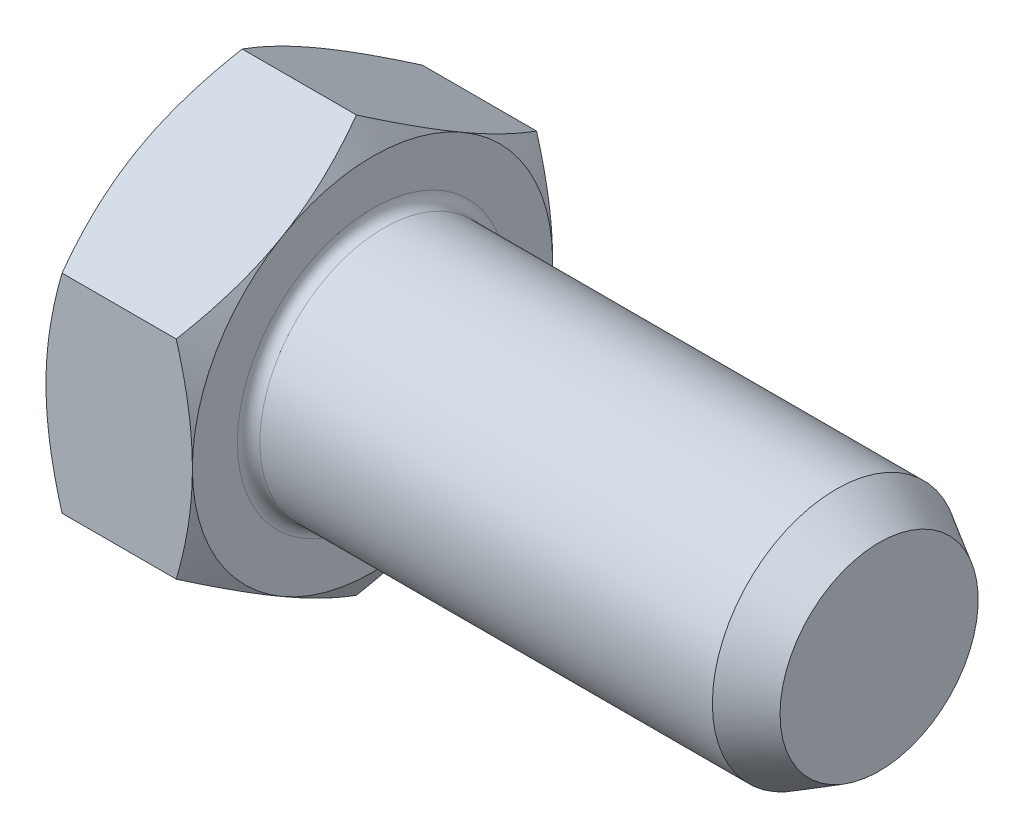
SolidWorks part; units mm, degrees
ref_plane "Front" through (0, 0, 0) normal (0, 0, 1) x (1, 0, 0)
ref_plane "Top" through (0, 0, 0) normal (0, 1, 0) x (1, 0, 0)
ref_plane "Right" through (0, 0, 0) normal (1, 0, 0) x (0, 0, -1)
sketch "Sketch1" plane through (0, 0, 0) normal (0, 0, 1) x (1, 0, 0)
  line L0 (0, 0) -> (0, 1.4)
  line L1 (0, 1.4) -> (1.3, 1.4)
  line L2 (1.3, 1.4) -> (1.3, 1.1)
  line L4 (1.3, 1.1) -> (5.8, 1.1)
  line L5 (5.8, 1.1) -> (5.8, 0)
  line L6 (5.8, 0) -> (0, 0)
  line L7 (13.1079, 0) -> (-2.2203, 0) construction
revolve "Revolve1" add sketch "Sketch1" angle 360 about L7
cosmetic thread "ThreadCosmetic" [suppressed] parameters "D2"=1.63
sketch "Sketch2" plane through (0, 0, 0) normal (-1, 0, 0) x (0, 0, 1)
  line L1 (1.6, -0.9238) -> (1.6, 0.9238)
  line L2 (1.6, 0.9238) -> (0, 1.8475)
  line L3 (0, 1.8475) -> (-1.6, 0.9238)
  line L4 (-1.6, 0.9238) -> (-1.6, -0.9238)
  line L5 (-1.6, -0.9238) -> (0, -1.8475)
  line L6 (0, -1.8475) -> (1.6, -0.9238)
  circle A0 centre (0, 0) radius 1.6 construction
extrude "Extrude1" add sketch "Sketch2" against normal blind 1.3
sketch "Sketch3" plane through (0, 0, 0) normal (0, 1, 0) x (1, 0, 0)
  line L0 (-0.9238, 0) -> (0.65, 2.7258)
  line L1 (0.65, 2.7258) -> (1.3, 1.6)
  line L2 (0, 0) -> (-2.2444, 0) construction
  line L4 (1.3, 1.6) -> (1.3, 3.2258)
  line L5 (1.3, 3.2258) -> (-1.0238, 3.2258)
  line L6 (-0.9238, 0) -> (-1.0238, 0)
  line L7 (-1.0238, 0) -> (-1.0238, 3.2258)
  dimension "D1" = 60
  dimension "D2" = 0.5
  dimension "D3" = 0.1
  dimension "D4" = 60
revolve "Cut-Revolve2" cut sketch "Sketch3" angle 360 about L2
sketch "Sketch4" plane through (0, 0, 0) normal (0, 0, 1) x (1, 0, 0)
  line L0 (0, 0) -> (1.9538, 0) construction
  line L1 (-0.2, 0) -> (-0.2, 1.28)
  line L2 (-0.2, 1.28) -> (0.4, 1.28)
  line L3 (0.4, 1.28) -> (0.4, 0)
  line L4 (1.3, 1.4) -> (1.3, 1.1) construction
  line L5 (1.3, 1.4) -> (1.3, 1.8049) construction
  line L6 (0.4, 0) -> (-0.2, 0)
  dimension "D1" = 0.2
  dimension "D2" = 2.56
revolve "Cut-Revolve3" cut sketch "Sketch4" angle 360 about L0
chamfer "Chamfer1" distance 0.22 angle 60 1 edges at (5.8, 0, -1.1) first distance on face at (5.8, 0, -1.1)
sketch "Sketch6" plane through (0, 0, 0) normal (0, 0, 1) x (1, 0, 0)
  line L0 (2.0155, 0.815) -> (1.5445, 0.815)
  line L1 (1.5445, 0.815) -> (1.38, 1.1)
  line L2 (2.0155, 0.815) -> (2.18, 1.1)
  line L3 (1.38, 1.1) -> (1.38, 1.35)
  line L4 (2.18, 1.1) -> (2.18, 1.35)
  line L5 (1.38, 1.35) -> (2.18, 1.35)
  line L6 (1.78, 0.815) -> (1.78, 0) construction
  line L7 (0, 0) -> (7.3035, 0) construction
  dimension "D2" = 60
  dimension "D3" = 0.25
  dimension "minordia" = 1.63
  dimension "threadstart" = 1.78
  dimension "D1" = 2.2
revolve "ThreadSchematic" [suppressed] cut sketch "Sketch6" angle 360 about L7
pattern_linear "ThdSchPat" [suppressed] count 6 spacing 0.8 along (1, 0, 0) of bodies 139
sketch "Sketch5" plane through (0, 0, 0) normal (0, 0, 1) x (1, 0, 0)
  line L1 (5.8, 1.1) -> (5.8, 0) construction
  line L3 (3.5, -1.1) -> (4, -1.1) construction
  line L4 (0, 0) -> (6.648, 0) construction
  line L5 (5.8, 0) -> (4, -1.1)
  line L6 (5.8, 0) -> (6, 0)
  line L7 (6, 0) -> (6, -1.3)
  line L8 (6, -1.3) -> (4, -1.3)
  line L9 (4, -1.3) -> (4, -1.1)
  line L10 (4, -1.1) -> (6.8602, -1.1) construction
  dimension "D1" = 0.2
  dimension "D3" = 0.2
  dimension "D4" = 2.2
  dimension "y" = 2
revolve "EndCone" [suppressed] cut sketch "Sketch5" angle 360 about L4
fillet "Fillet1" radius 0.1 1 edges at (1.3, 0, -1.1)
equation "\"minordia@Sketch6\" = \"D2@ThreadCosmetic\""
equation "\"D1@Extrude1\" = \"k@Sketch1\""
equation "\"D2@Sketch4\" = \"s@Sketch2\" * 4 / 5"
equation "\"D1@Chamfer1\" = \"d@Sketch1\" / 10"
equation "\"threadstart@Sketch6\" = \"D1@Extrude1\"+(\"advance@Sketch6\"*0.6)"
equation "\"D1@ThdSchPat\" = int((\"l@Sketch1\"/\"advance@Sketch6\") + 0.8)"
equation "\"D3@ThdSchPat\" = \"advance@Sketch6\""
equation "\"D1@Sketch6\" = \"d@Sketch1\""
equation "\"D4@Sketch5\" = \"d@Sketch1\""
